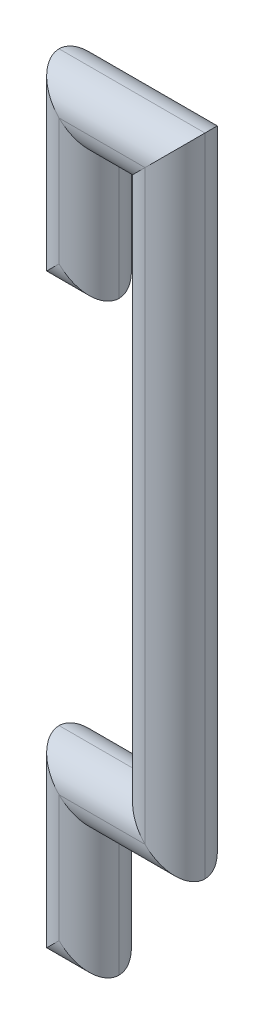
SolidWorks part; units mm, degrees
ref_plane "Plan de face" through (0, 0, 0) normal (0, 0, 1) x (1, 0, 0)
ref_plane "Plan de dessus" through (0, 0, 0) normal (0, 1, 0) x (1, 0, 0)
ref_plane "Plan de droite" through (0, 0, 0) normal (1, 0, 0) x (0, 0, -1)
sketch "Esquisse1" plane through (0, 0, 0) normal (0, 0, 1) x (1, 0, 0)
  line L0 (0, 0) -> (-6.6, 0)
  line L1 (-6.6, 0) -> (-6.6, -12)
  line L2 (0, 0) -> (0, -45)
  line L3 (0, -45) -> (-6.6, -45)
  line L4 (-6.6, -45) -> (-6.6, -57)
  point P7 (-12.3056, -15.3824)
  dimension "D1" = 45
  dimension "D2" = 12
  dimension "D3" = 6.6
extrude "Extru.-Mince1" add sketch "Esquisse1" along normal mid plane 4.6 thin
fillet "Congé1" radius 2.3 24 edges at (-6.6, -57, -2.3) (-4.3, -52.15, -2.3) (-1, -47.3, -2.3) (2.3, -22.5, -2.3) (-3.3, 2.3, -2.3) (-8.9, -4.85, -2.3) (-6.6, -12, -2.3) (-4.3, -7.15, -2.3) (-3.3, -2.3, -2.3) (-2.3, -22.5, -2.3) (-5.6, -42.7, -2.3) (-8.9, -49.85, -2.3) (-5.6, -42.7, 2.3) (-2.3, -22.5, 2.3) (-3.3, -2.3, 2.3) (-4.3, -7.15, 2.3) (-6.6, -12, 2.3) (-8.9, -4.85, 2.3) (-3.3, 2.3, 2.3) (2.3, -22.5, 2.3) (-1, -47.3, 2.3) (-4.3, -52.15, 2.3) (-6.6, -57, 2.3) (-8.9, -49.85, 2.3)
